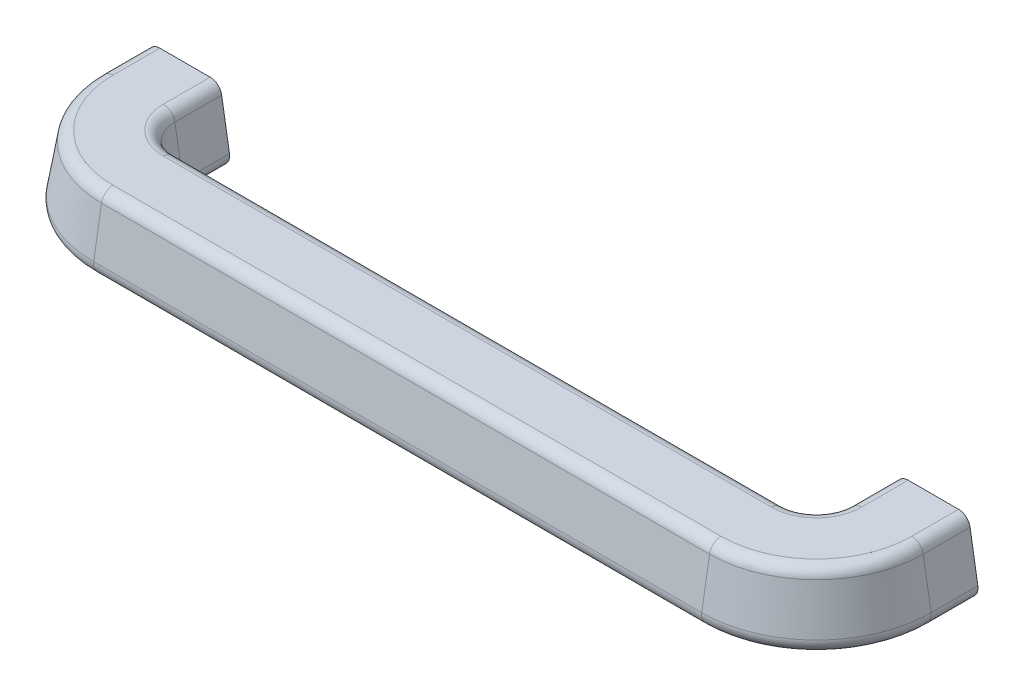
SolidWorks part; units mm, degrees
material "ABS PC"
ref_plane "Front Plane" through (0, 0, 0) normal (0, 0, 1) x (1, 0, 0)
ref_plane "Top Plane" through (0, 0, 0) normal (0, 1, 0) x (1, 0, 0)
ref_plane "Right Plane" through (0, 0, 0) normal (1, 0, 0) x (0, 0, -1)
sketch "Sketch1" plane through (0, 0, 0) normal (0, 1, 0) x (1, 0, 0)
  line L0 (-165.1, 0) -> (165.1, 0)
  line L1 (-203.2, 38.1) -> (-203.2, 63.5)
  line L2 (203.2, 38.1) -> (203.2, 63.5)
  arc A0 (-165.1, 0) -> (-203.2, 38.1) centre (-165.1, 38.1) cw
  arc A1 (165.1, 0) -> (203.2, 38.1) centre (165.1, 38.1) ccw
  point P6 (-203.2, 0)
  point P9 (203.2, 0)
  dimension "D2" = 38.1
  dimension "D1" = 406.4
  dimension "D3" = 63.5
ref_plane "Plane1" through (203.2, 0, -63.5) normal (0, 0, -1) x (-1, 0, 0)
sketch "Sketch2" plane through (203.2, 0, -63.5) normal (0, 0, -1) x (-1, 0, 0)
  line L0 (-13.6707, 19.05) -> (13.6707, 19.05)
  line L1 (-17.9041, -19.05) -> (17.9041, -19.05)
  line L2 (24.1677, -11.6561) -> (19.9343, 13.7439)
  line L3 (-19.9343, 13.7439) -> (-24.1677, -11.6561)
  line L4 (0, 19.05) -> (0, -19.05) construction
  line L6 (-12.7, -12.7) -> (12.7, -12.7)
  line L7 (-12.7, -12.7) -> (-12.7, 12.7)
  line L8 (-12.7, 12.7) -> (12.7, 12.7)
  line L9 (12.7, -12.7) -> (12.7, 12.7)
  line L10 (-12.7, -12.7) -> (12.7, 12.7) construction
  line L11 (-12.7, 12.7) -> (12.7, -12.7) construction
  arc A0 (-13.6707, 19.05) -> (-19.9343, 13.7439) centre (-13.6707, 12.7) ccw
  arc A1 (13.6707, 19.05) -> (19.9343, 13.7439) centre (13.6707, 12.7) cw
  arc A2 (17.9041, -19.05) -> (24.1677, -11.6561) centre (17.9041, -12.7) ccw
  arc A3 (-17.9041, -19.05) -> (-24.1677, -11.6561) centre (-17.9041, -12.7) cw
  point P8 (-19.05, 19.05)
  point P11 (19.05, 19.05)
  point P14 (25.4, -19.05)
  point P17 (-25.4, -19.05)
  point P19 (0, 0)
  dimension "D4" = 6.35
  dimension "D1" = 38.1
  dimension "D2" = 50.8
  dimension "D3" = 38.1
  dimension "D5" = 25.4
sweep "Sweep1" add profiles "Sketch2" path "Sketch1"
